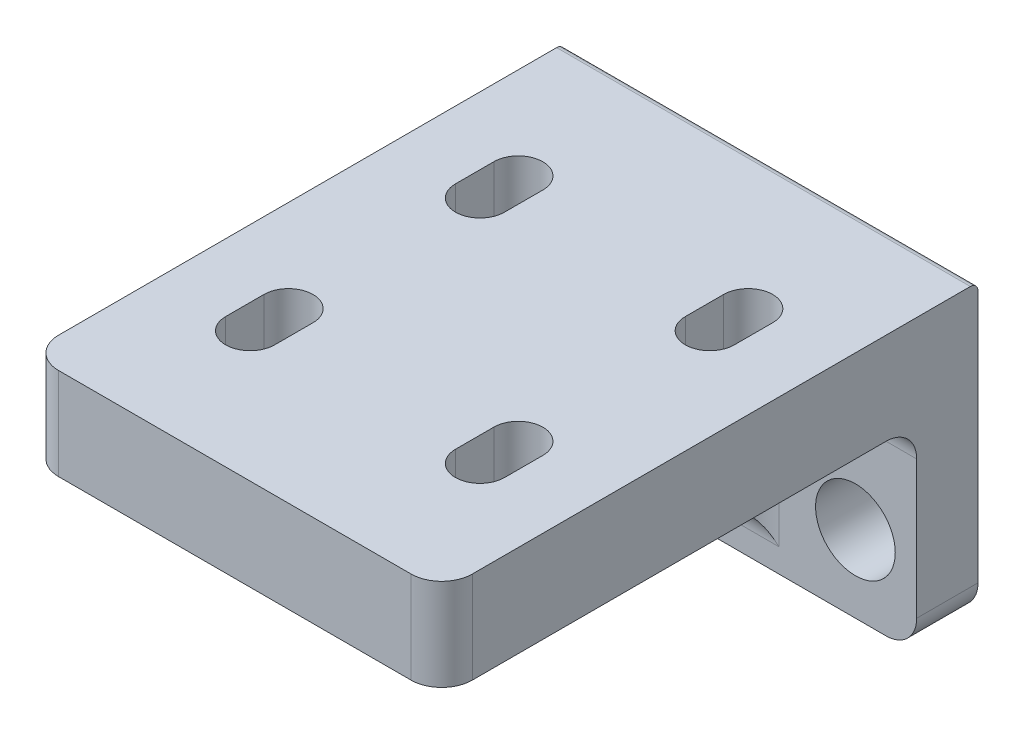
SolidWorks part; units mm, degrees
ref_plane "前视基准面" through (0, 0, 0) normal (0, 0, 1) x (1, 0, 0)
ref_plane "上视基准面" through (0, 0, 0) normal (0, 1, 0) x (1, 0, 0)
ref_plane "右视基准面" through (0, 0, 0) normal (1, 0, 0) x (0, 0, -1)
sketch "草图1" plane through (0, 0, 0) normal (0, 0, 1) x (1, 0, 0)
  line L1 (0, 0) -> (27, 0)
  line L2 (0, 0) -> (0, -16)
  line L3 (0, -16) -> (27, -16)
  line L4 (27, 0) -> (27, -16)
  dimension "D1" = 16
  dimension "D2" = 2
  dimension "D3" = 27
extrude "凸台-拉伸2" add sketch "草图1" along normal blind 3 and the other way blind 1 contours L2 L1 L4 L3
sketch "草图3" plane through (0, 0, 0) normal (0, 1, 0) x (1, 0, 0)
  line L0 (27, -3) -> (27, 1) construction
  line L1 (0, 0) -> (27, 0)
  line L2 (0, 0) -> (0, -34)
  line L3 (0, -34) -> (27, -34)
  line L4 (27, 0) -> (27, -34)
  dimension "D1" = 34
extrude "凸台-拉伸4" add sketch "草图3" against normal blind 3 and the other way blind 3
sketch "草图4" plane through (0, -3, 0) normal (0, -1, 0) x (-1, 0, 0)
  line L0 (-6, -10.5) -> (-6, -8) construction
  line L1 (-7.6, -10.5) -> (-7.6, -8)
  line L2 (-4.4, -10.5) -> (-4.4, -8)
  line L3 (-21, -10.5) -> (-21, -8) construction
  line L4 (-22.6, -10.5) -> (-22.6, -8)
  line L5 (-19.4, -10.5) -> (-19.4, -8)
  line L6 (-6, -25.5) -> (-6, -23) construction
  line L7 (-7.6, -25.5) -> (-7.6, -23)
  line L8 (-4.4, -25.5) -> (-4.4, -23)
  line L9 (-21, -25.5) -> (-21, -23) construction
  line L10 (-22.6, -25.5) -> (-22.6, -23)
  line L11 (-19.4, -25.5) -> (-19.4, -23)
  line L12 (0, -3) -> (0, -34) construction
  line L13 (-27, -34) -> (-27, -3) construction
  arc A0 (-7.6, -10.5) -> (-4.4, -10.5) centre (-6, -10.5) ccw
  arc A1 (-4.4, -8) -> (-7.6, -8) centre (-6, -8) ccw
  arc A2 (-22.6, -10.5) -> (-19.4, -10.5) centre (-21, -10.5) ccw
  arc A3 (-19.4, -8) -> (-22.6, -8) centre (-21, -8) ccw
  arc A4 (-7.6, -25.5) -> (-4.4, -25.5) centre (-6, -25.5) ccw
  arc A5 (-4.4, -23) -> (-7.6, -23) centre (-6, -23) ccw
  arc A6 (-22.6, -25.5) -> (-19.4, -25.5) centre (-21, -25.5) ccw
  arc A7 (-19.4, -23) -> (-22.6, -23) centre (-21, -23) ccw
  point P2 (-6, -9.25)
  point P11 (-21, -9.25)
  point P18 (-6, -24.25)
  point P25 (-21, -24.25)
  dimension "D1" = 2
  dimension "D6" = 1.6
  dimension "D3" = 31
  dimension "D4" = 4.4
  dimension "D5" = 11.8
  dimension "D2" = 2
extrude "切除-拉伸11" cut sketch "草图4" against normal blind 13
sketch "草图8" plane through (0, -3, 0) normal (0, -1, 0) x (-1, 0, 0)
  line L0 (0, -34) -> (-27, -34) construction
  point P0 (-13.5, -34)
sketch "草图9" plane through (0, 0, 3) normal (0, 0, 1) x (1, 0, 0)
  line L0 (0, -16) -> (27, -16) construction
  point P0 (13.5, -16)
sketch "草图12" plane through (0, 0, 3) normal (0, 0, 1) x (1, 0, 0)
  point P0 (13.5, -3)
ref_plane "基准面4" through (13.5, 0, 0) normal (-1, 0, 0) x (0, 0, 1)
sketch "草图13" plane through (13.5, 0, 0) normal (-1, 0, 0) x (0, 0, 1)
  line L0 (3, -13) -> (34, -3)
  line L2 (3, -13) -> (3, -3)
  line L3 (3, -3) -> (34, -3)
extrude "凸台-拉伸5" add sketch "草图13" against normal blind 2.5 and the other way blind 2.5
fillet "圆角2" radius 2 6 edges at (5.5, -3, 3) (21.5, -3, 3) (0, -16, 1) (27, -16, 1) (27, 0, 34) (0, 0, 34)
fillet "圆角3" radius 2 7 edges at (13.5, -13, 3) (16, -3, 19.5) (16, -3.5858, 3.5858) (16, -9, 3) (11, -9, 3) (11, -3, 19.5) (11, -3.5858, 3.5858)
sketch "草图14" plane through (0, 0, 0) normal (0, 0, -1) x (-1, 0, 0)
  line L1 (-27, 3) -> (0, 3)
  line L2 (-27, 3) -> (-27, 0)
  line L3 (-27, 0) -> (0, 0)
  line L4 (0, 3) -> (0, 0)
extrude "凸台-拉伸6" add sketch "草图14" along normal blind 1
fillet "圆角5" radius 0.5 1 edges at (13.5, 3, -1)
sketch "草图16" plane through (0, 0, 3) normal (0, 0, 1) x (1, 0, 0)
  line L0 (0, -5) -> (0, -14) construction
  line L1 (9, -5) -> (0, -5) construction
  line L2 (27, -5) -> (27, -14) construction
  line L3 (27, -5) -> (18, -5) construction
  circle A0 centre (4, -11) radius 2.6
  circle A3 centre (23, -11) radius 2.6
  dimension "D1" = 4
  dimension "D2" = 6
  dimension "D5" = 4
  dimension "D8" = 6
extrude "切除-拉伸12" cut sketch "草图16" against normal blind 4
